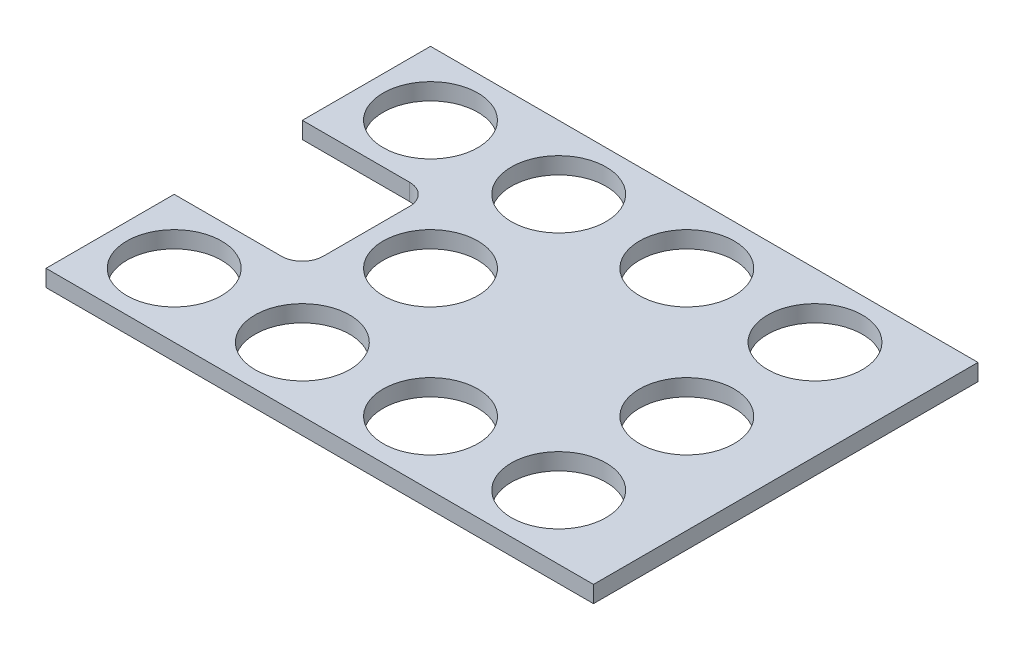
SolidWorks part; units mm, degrees
material "Pine"
ref_plane "Front Plane" through (0, 0, 0) normal (0, 0, 1) x (1, 0, 0)
ref_plane "Top Plane" through (0, 0, 0) normal (0, 1, 0) x (1, 0, 0)
ref_plane "Right Plane" through (0, 0, 0) normal (1, 0, 0) x (0, 0, -1)
sketch "Sketch1" plane through (0, 0, 0) normal (0, 1, 0) x (1, 0, 0)
  line L0 (46, 46) -> (264.076, 46)
  line L1 (0, 0) -> (393, 0)
  line L2 (0, 0) -> (0, 276)
  line L3 (0, 276) -> (393, 276)
  line L4 (393, 0) -> (393, 276)
  line L6 (0, 184) -> (77, 184)
  line L7 (0, 184) -> (0, 92)
  line L8 (0, 92) -> (77, 92)
  line L9 (92, 169) -> (92, 107)
  circle A0 centre (46, 46) radius 34
  circle A1 centre (46, 230) radius 34
  arc A2 (77, 92) -> (92, 107) centre (77, 107) ccw
  arc A3 (77, 184) -> (92, 169) centre (77, 169) cw
  circle A4 centre (138, 138) radius 34
  circle A5 centre (322, 138) radius 34
  point P21 (164.6325, 120.9325)
  point P22 (0, 0)
  point P25 (328.8199, 138)
  point P26 (0, 0)
  point P27 (0, 0)
  dimension "D1" = 46
  dimension "D2" = 68
  dimension "D9" = 15
  dimension "D12" = 138
  dimension "D3" = 393
  dimension "D4" = 276
  dimension "D5" = 46
  dimension "D6" = 46
  dimension "D7" = 46
  dimension "D8" = 92
  dimension "D10" = 92
  dimension "D11" = 92
  dimension "D13" = 138
  dimension "D14" = 184
  dimension "D15" = 138
extrude "Boss-Extrude1" add sketch "Sketch1" along normal blind 12 contours L2 L3 L4 L1
extrude "Cut-Extrude1" cut sketch "Sketch1<3>" along normal up to surface (12 mm away) contours A0 | A1 up to face at (196.5, 12, -138)
sketch "Sketch1<3>" plane through (0, 0, 0) normal (0, 1, 0) x (1, 0, 0) same geometry as "Sketch1"
pattern_linear "LPattern1" count 4 spacing 92 along (1, 0, 0) of "Cut-Extrude1"
extrude "Cut-Extrude3" cut sketch "Sketch1<4>" along normal up to surface (12 mm away) contours A3 L6 L2 L8 A2 L9 | A4 | A5 region at (45.5078, 0, -138) region at (138, 0, -138) region at (322, 0, -138) up to face at (322, 12, -12)
sketch "Sketch1<4>" plane through (0, 0, 0) normal (0, 1, 0) x (1, 0, 0) same geometry as "Sketch1"
